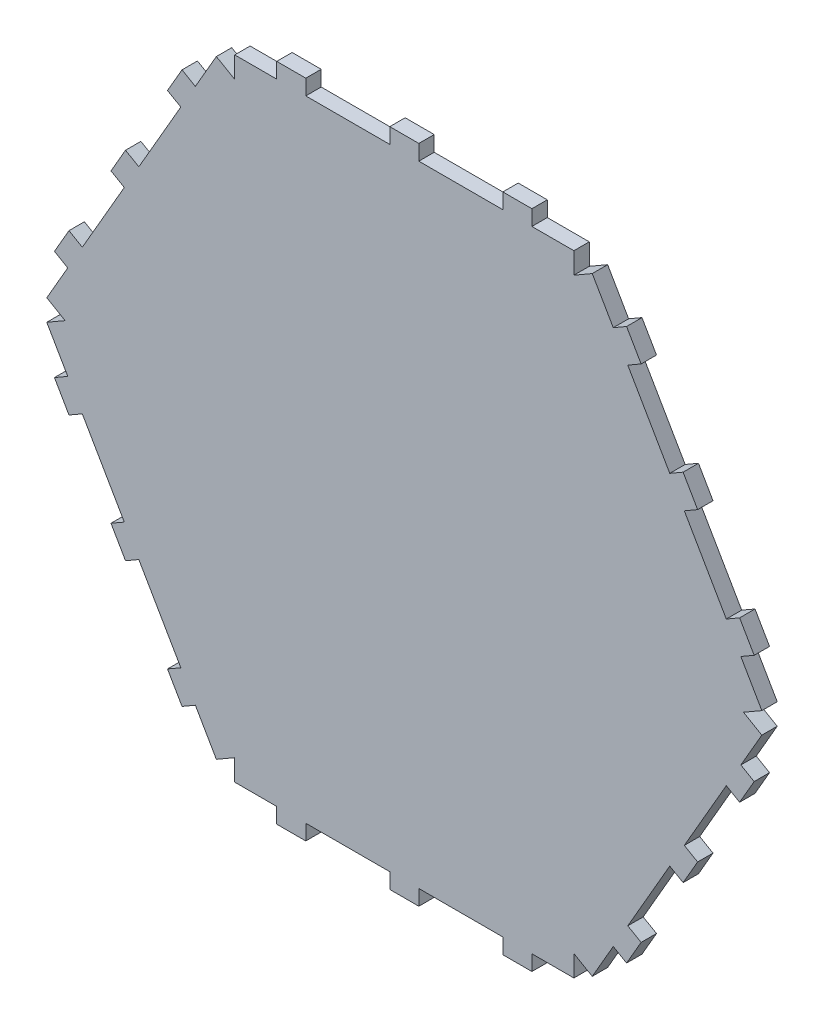
SolidWorks part; units mm, degrees
ref_plane "Front Plane" through (0, 0, 0) normal (0, 0, 1) x (1, 0, 0)
ref_plane "Top Plane" through (0, 0, 0) normal (0, 1, 0) x (1, 0, 0)
ref_plane "Right Plane" through (0, 0, 0) normal (1, 0, 0) x (0, 0, -1)
sketch "Sketch2" plane through (0, 0, 0) normal (0, 0, 1) x (1, 0, 0)
  line L0 (-35, 65) -> (-35, 60.6218)
  line L1 (35, 65) -> (35, 60.6218)
  line L2 (-35, 65) -> (-11.6667, 65) construction
  line L3 (-35, 60.6218) -> (35, 60.6218) construction
  line L4 (35, 60.6218) -> (70, 0) construction
  line L5 (70, 0) -> (35, -60.6218) construction
  line L6 (35, -60.6218) -> (-35, -60.6218) construction
  line L7 (0, 87.3633) -> (0, -0.0109) construction
  line L8 (0, 0) -> (44.1971, 0) construction
  line L9 (-11.6667, 65) -> (11.6667, 65) construction
  line L10 (11.6667, 65) -> (35, 65) construction
  line L11 (-23.3333, 65) -> (-23.3333, 68.175) construction
  line L12 (-20.3333, 68.175) -> (-26.3333, 68.175)
  line L13 (-35, -60.6218) -> (-70, 0) construction
  line L14 (-70, 0) -> (-35, 60.6218) construction
  line L15 (-70, 0) -> (59.0387, 0)
  line L16 (-26.3333, 68.175) -> (-26.3333, 65)
  line L17 (-26.3333, 68.175) -> (-20.3333, 68.175)
  line L18 (-20.3333, 68.175) -> (-20.3333, 65)
  line L19 (-11.6667, 137.7104) -> (-11.6667, 152.546) construction
  line L20 (11.6667, 137.7104) -> (11.6667, 152.546) construction
  line L21 (-26.3333, 68.175) -> (-26.3333, 65)
  line L22 (-20.3333, 68.175) -> (-20.3333, 65)
  line L23 (-26.3333, 68.175) -> (-26.3333, 65)
  line L24 (-20.3333, 68.175) -> (-20.3333, 65)
  line L25 (-26.3333, 68.175) -> (-26.3333, 65)
  line L26 (-20.3333, 68.175) -> (-20.3333, 65)
  line L27 (-26.3333, 68.175) -> (-26.3333, 65)
  line L28 (-20.3333, 68.175) -> (-20.3333, 65)
  line L29 (-26.3333, 68.175) -> (-26.3333, 65)
  line L30 (-20.3333, 68.175) -> (-20.3333, 65)
  line L31 (-26.3333, 68.175) -> (-26.3333, 65)
  line L32 (-20.3333, 68.175) -> (-20.3333, 65)
  line L33 (-26.3333, 68.175) -> (-26.3333, 65)
  line L34 (-20.3333, 68.175) -> (-20.3333, 65)
  line L35 (-26.3333, 68.175) -> (-26.3333, 65)
  line L36 (-20.3333, 68.175) -> (-20.3333, 65)
  line L37 (-26.3333, 68.175) -> (-26.3333, 65)
  line L38 (-20.3333, 68.175) -> (-20.3333, 65)
  line L39 (-26.3333, 68.175) -> (-26.3333, 65)
  line L40 (-20.3333, 68.175) -> (-20.3333, 65)
  line L41 (-26.3333, 68.175) -> (-26.3333, 65)
  line L42 (-20.3333, 68.175) -> (-20.3333, 65)
  line L43 (-26.3333, 68.175) -> (-26.3333, 65)
  line L44 (-20.3333, 68.175) -> (-20.3333, 65)
  line L45 (-26.3333, 68.175) -> (-26.3333, 65)
  line L46 (-20.3333, 68.175) -> (-20.3333, 65)
  line L47 (-26.3333, 68.175) -> (-26.3333, 65)
  line L48 (-20.3333, 68.175) -> (-20.3333, 65)
  line L49 (-26.3333, 68.175) -> (-26.3333, 65)
  line L50 (-20.3333, 68.175) -> (-20.3333, 65)
  line L51 (-26.3333, 68.175) -> (-26.3333, 65)
  line L52 (-20.3333, 68.175) -> (-20.3333, 65)
  line L53 (-26.3333, 68.175) -> (-26.3333, 65)
  line L54 (-20.3333, 68.175) -> (-20.3333, 65)
  line L55 (-26.3333, 68.175) -> (-26.3333, 65)
  line L56 (-20.3333, 68.175) -> (-20.3333, 65)
  line L57 (-26.3333, 68.175) -> (-26.3333, 65)
  line L58 (-20.3333, 68.175) -> (-20.3333, 65)
  line L59 (-26.3333, 68.175) -> (-26.3333, 65)
  line L60 (-20.3333, 68.175) -> (-20.3333, 65)
  line L61 (-26.3333, 68.175) -> (-26.3333, 65)
  line L62 (-20.3333, 68.175) -> (-20.3333, 65)
  line L63 (-26.3333, 68.175) -> (-26.3333, 65)
  line L64 (-20.3333, 68.175) -> (-20.3333, 65)
  line L65 (-26.3333, 68.175) -> (-26.3333, 65)
  line L66 (-20.3333, 68.175) -> (-20.3333, 65)
  line L67 (-26.3333, 68.175) -> (-26.3333, 65)
  line L68 (-20.3333, 68.175) -> (-20.3333, 65)
  line L69 (-26.3333, 68.175) -> (-26.3333, 65)
  line L70 (-20.3333, 68.175) -> (-20.3333, 65)
  line L71 (-26.3333, 68.175) -> (-26.3333, 65)
  line L72 (-20.3333, 68.175) -> (-20.3333, 65)
  line L73 (-26.3333, 68.175) -> (-26.3333, 65)
  line L74 (-20.3333, 68.175) -> (-20.3333, 65)
  line L75 (-26.3333, 68.175) -> (-26.3333, 65)
  line L76 (-20.3333, 68.175) -> (-20.3333, 65)
  line L77 (-26.3333, 68.175) -> (-26.3333, 65)
  line L78 (-20.3333, 68.175) -> (-20.3333, 65)
  line L79 (-26.3333, 68.175) -> (-26.3333, 65)
  line L80 (-20.3333, 68.175) -> (-20.3333, 65)
  line L81 (-26.3333, 68.175) -> (-26.3333, 65)
  line L82 (-20.3333, 68.175) -> (-20.3333, 65)
  line L83 (0, 65) -> (0, 68.175) construction
  line L84 (-3, 68.175) -> (-3, 65)
  line L85 (3, 68.175) -> (3, 65)
  line L86 (-3, 68.175) -> (-3, 65)
  line L87 (3, 68.175) -> (3, 65)
  line L88 (-3, 68.175) -> (-3, 65)
  line L89 (3, 68.175) -> (3, 65)
  line L90 (-3, 68.175) -> (-3, 65)
  line L91 (3, 68.175) -> (3, 65)
  line L92 (-3, 68.175) -> (-3, 65)
  line L93 (3, 68.175) -> (3, 65)
  line L94 (-3, 68.175) -> (-3, 65)
  line L95 (3, 68.175) -> (3, 65)
  line L96 (-3, 68.175) -> (-3, 65)
  line L97 (3, 68.175) -> (3, 65)
  line L98 (-3, 68.175) -> (-3, 65)
  line L99 (3, 68.175) -> (3, 65)
  line L100 (-3, 68.175) -> (-3, 65)
  line L101 (3, 68.175) -> (3, 65)
  line L102 (-3, 68.175) -> (-3, 65)
  line L103 (3, 68.175) -> (3, 65)
  line L104 (-3, 68.175) -> (-3, 65)
  line L105 (3, 68.175) -> (3, 65)
  line L106 (-3, 68.175) -> (-3, 65)
  line L107 (3, 68.175) -> (3, 65)
  line L108 (-3, 68.175) -> (-3, 65)
  line L109 (3, 68.175) -> (3, 65)
  line L110 (-3, 68.175) -> (-3, 65)
  line L111 (3, 68.175) -> (3, 65)
  line L112 (-3, 68.175) -> (-3, 65)
  line L113 (3, 68.175) -> (3, 65)
  line L114 (-3, 68.175) -> (-3, 65)
  line L115 (3, 68.175) -> (3, 65)
  line L116 (-3, 68.175) -> (-3, 65)
  line L117 (3, 68.175) -> (3, 65)
  line L118 (-3, 68.175) -> (-3, 65)
  line L119 (3, 68.175) -> (3, 65)
  line L120 (-3, 68.175) -> (-3, 65)
  line L121 (3, 68.175) -> (3, 65)
  line L122 (-3, 68.175) -> (-3, 65)
  line L123 (3, 68.175) -> (3, 65)
  line L124 (-3, 68.175) -> (-3, 65)
  line L125 (3, 68.175) -> (3, 65)
  line L126 (-3, 68.175) -> (-3, 65)
  line L127 (3, 68.175) -> (3, 65)
  line L128 (-3, 68.175) -> (-3, 65)
  line L129 (3, 68.175) -> (3, 65)
  line L130 (-3, 68.175) -> (-3, 65)
  line L131 (3, 68.175) -> (3, 65)
  line L132 (-3, 68.175) -> (-3, 65)
  line L133 (3, 68.175) -> (3, 65)
  line L134 (-3, 68.175) -> (-3, 65)
  line L135 (3, 68.175) -> (3, 65)
  line L136 (-3, 68.175) -> (-3, 65)
  line L137 (3, 68.175) -> (3, 65)
  line L138 (-3, 68.175) -> (-3, 65)
  line L139 (3, 68.175) -> (3, 65)
  line L140 (-3, 68.175) -> (-3, 65)
  line L141 (3, 68.175) -> (3, 65)
  line L142 (-3, 68.175) -> (-3, 65)
  line L143 (3, 68.175) -> (3, 65)
  line L144 (-3, 68.175) -> (-3, 65)
  line L145 (3, 68.175) -> (3, 65)
  line L146 (-3, 68.175) -> (-3, 65)
  line L147 (3, 68.175) -> (-3, 68.175)
  line L148 (3, 68.175) -> (3, 65)
  line L149 (-3, 68.175) -> (3, 68.175)
  line L150 (-3, 68.175) -> (-3, 65)
  line L151 (3, 68.175) -> (3, 65)
  line L152 (-3, 68.175) -> (-3, 65)
  line L153 (3, 68.175) -> (3, 65)
  line L154 (-3, 68.175) -> (-3, 65)
  line L155 (3, 68.175) -> (3, 65)
  line L156 (-3, 68.175) -> (-3, 65)
  line L157 (3, 68.175) -> (3, 65)
  line L158 (-3, 68.175) -> (-3, 65)
  line L159 (3, 68.175) -> (3, 65)
  line L160 (-3, 68.175) -> (-3, 65)
  line L161 (3, 68.175) -> (3, 65)
  line L162 (-3, 68.175) -> (-3, 65)
  line L163 (3, 68.175) -> (3, 65)
  line L164 (-3, 68.175) -> (-3, 65)
  line L165 (3, 68.175) -> (3, 65)
  line L166 (-3, 68.175) -> (-3, 65)
  line L167 (3, 68.175) -> (3, 65)
  line L168 (-3, 68.175) -> (-3, 65)
  line L169 (3, 68.175) -> (3, 65)
  line L170 (-3, 68.175) -> (-3, 65)
  line L171 (3, 68.175) -> (3, 65)
  line L172 (-3, 68.175) -> (-3, 65)
  line L173 (3, 68.175) -> (3, 65)
  line L174 (-3, 68.175) -> (-3, 65)
  line L175 (3, 68.175) -> (3, 65)
  line L176 (-3, 68.175) -> (-3, 65)
  line L177 (3, 68.175) -> (3, 65)
  line L178 (-3, 68.175) -> (-3, 65)
  line L179 (3, 68.175) -> (3, 65)
  line L180 (-3, 68.175) -> (-3, 65)
  line L181 (3, 68.175) -> (3, 65)
  line L182 (-3, 68.175) -> (-3, 65)
  line L183 (3, 68.175) -> (3, 65)
  line L184 (-3, 68.175) -> (-3, 65)
  line L185 (3, 68.175) -> (3, 65)
  line L186 (-3, 68.175) -> (-3, 65)
  line L187 (3, 68.175) -> (3, 65)
  line L188 (-3, 68.175) -> (-3, 65)
  line L189 (3, 68.175) -> (3, 65)
  line L190 (-3, 68.175) -> (-3, 65)
  line L191 (3, 68.175) -> (3, 65)
  line L192 (-3, 68.175) -> (-3, 65)
  line L193 (3, 68.175) -> (3, 65)
  line L194 (-3, 68.175) -> (-3, 65)
  line L195 (3, 68.175) -> (3, 65)
  line L196 (-3, 68.175) -> (-3, 65)
  line L197 (3, 68.175) -> (3, 65)
  line L198 (-3, 68.175) -> (-3, 65)
  line L199 (3, 68.175) -> (3, 65)
  line L200 (-3, 68.175) -> (-3, 65)
  line L201 (3, 68.175) -> (3, 65)
  line L202 (-3, 68.175) -> (-3, 65)
  line L203 (3, 68.175) -> (3, 65)
  line L204 (-3, 68.175) -> (-3, 65)
  line L205 (3, 68.175) -> (3, 65)
  line L206 (-3, 68.175) -> (-3, 65)
  line L207 (3, 68.175) -> (3, 65)
  line L208 (-3, 68.175) -> (-3, 65)
  line L209 (3, 68.175) -> (3, 65)
  line L210 (-3, 68.175) -> (-3, 65)
  line L211 (3, 68.175) -> (3, 65)
  line L212 (-3, 68.175) -> (-3, 65)
  line L213 (3, 68.175) -> (3, 65)
  line L214 (23.3333, 65) -> (23.3333, 68.175) construction
  line L215 (20.3333, 68.175) -> (20.3333, 65)
  line L216 (26.3333, 68.175) -> (26.3333, 65)
  line L217 (20.3333, 68.175) -> (20.3333, 65)
  line L218 (26.3333, 68.175) -> (26.3333, 65)
  line L219 (20.3333, 68.175) -> (20.3333, 65)
  line L220 (26.3333, 68.175) -> (26.3333, 65)
  line L221 (20.3333, 68.175) -> (20.3333, 65)
  line L222 (26.3333, 68.175) -> (26.3333, 65)
  line L223 (20.3333, 68.175) -> (20.3333, 65)
  line L224 (26.3333, 68.175) -> (26.3333, 65)
  line L225 (20.3333, 68.175) -> (20.3333, 65)
  line L226 (26.3333, 68.175) -> (26.3333, 65)
  line L227 (20.3333, 68.175) -> (20.3333, 65)
  line L228 (26.3333, 68.175) -> (26.3333, 65)
  line L229 (20.3333, 68.175) -> (20.3333, 65)
  line L230 (26.3333, 68.175) -> (26.3333, 65)
  line L231 (20.3333, 68.175) -> (20.3333, 65)
  line L232 (26.3333, 68.175) -> (26.3333, 65)
  line L233 (20.3333, 68.175) -> (20.3333, 65)
  line L234 (26.3333, 68.175) -> (26.3333, 65)
  line L235 (20.3333, 68.175) -> (20.3333, 65)
  line L236 (26.3333, 68.175) -> (26.3333, 65)
  line L237 (20.3333, 68.175) -> (20.3333, 65)
  line L238 (26.3333, 68.175) -> (26.3333, 65)
  line L239 (20.3333, 68.175) -> (20.3333, 65)
  line L240 (26.3333, 68.175) -> (26.3333, 65)
  line L241 (20.3333, 68.175) -> (20.3333, 65)
  line L242 (26.3333, 68.175) -> (26.3333, 65)
  line L243 (20.3333, 68.175) -> (20.3333, 65)
  line L244 (26.3333, 68.175) -> (26.3333, 65)
  line L245 (20.3333, 68.175) -> (20.3333, 65)
  line L246 (26.3333, 68.175) -> (26.3333, 65)
  line L247 (20.3333, 68.175) -> (20.3333, 65)
  line L248 (26.3333, 68.175) -> (26.3333, 65)
  line L249 (20.3333, 68.175) -> (20.3333, 65)
  line L250 (26.3333, 68.175) -> (26.3333, 65)
  line L251 (20.3333, 68.175) -> (20.3333, 65)
  line L252 (26.3333, 68.175) -> (26.3333, 65)
  line L253 (20.3333, 68.175) -> (20.3333, 65)
  line L254 (26.3333, 68.175) -> (26.3333, 65)
  line L255 (20.3333, 68.175) -> (20.3333, 65)
  line L256 (26.3333, 68.175) -> (26.3333, 65)
  line L257 (20.3333, 68.175) -> (20.3333, 65)
  line L258 (26.3333, 68.175) -> (26.3333, 65)
  line L259 (20.3333, 68.175) -> (20.3333, 65)
  line L260 (26.3333, 68.175) -> (26.3333, 65)
  line L261 (20.3333, 68.175) -> (20.3333, 65)
  line L262 (26.3333, 68.175) -> (26.3333, 65)
  line L263 (20.3333, 68.175) -> (20.3333, 65)
  line L264 (26.3333, 68.175) -> (26.3333, 65)
  line L265 (20.3333, 68.175) -> (20.3333, 65)
  line L266 (26.3333, 68.175) -> (26.3333, 65)
  line L267 (20.3333, 68.175) -> (20.3333, 65)
  line L268 (26.3333, 68.175) -> (26.3333, 65)
  line L269 (20.3333, 68.175) -> (20.3333, 65)
  line L270 (26.3333, 68.175) -> (26.3333, 65)
  line L271 (20.3333, 68.175) -> (20.3333, 65)
  line L272 (26.3333, 68.175) -> (26.3333, 65)
  line L273 (20.3333, 68.175) -> (20.3333, 65)
  line L274 (26.3333, 68.175) -> (26.3333, 65)
  line L275 (20.3333, 68.175) -> (20.3333, 65)
  line L276 (26.3333, 68.175) -> (26.3333, 65)
  line L277 (20.3333, 68.175) -> (20.3333, 65)
  line L278 (26.3333, 68.175) -> (26.3333, 65)
  line L279 (26.3333, 68.175) -> (20.3333, 68.175)
  line L280 (20.3333, 68.175) -> (20.3333, 65)
  line L281 (20.3333, 68.175) -> (26.3333, 68.175)
  line L282 (26.3333, 68.175) -> (26.3333, 65)
  line L283 (20.3333, 68.175) -> (20.3333, 65)
  line L284 (26.3333, 68.175) -> (26.3333, 65)
  line L285 (20.3333, 68.175) -> (20.3333, 65)
  line L286 (26.3333, 68.175) -> (26.3333, 65)
  line L287 (20.3333, 68.175) -> (20.3333, 65)
  line L288 (26.3333, 68.175) -> (26.3333, 65)
  line L289 (20.3333, 68.175) -> (20.3333, 65)
  line L290 (26.3333, 68.175) -> (26.3333, 65)
  line L291 (20.3333, 68.175) -> (20.3333, 65)
  line L292 (26.3333, 68.175) -> (26.3333, 65)
  line L293 (20.3333, 68.175) -> (20.3333, 65)
  line L294 (26.3333, 68.175) -> (26.3333, 65)
  line L295 (20.3333, 68.175) -> (20.3333, 65)
  line L296 (26.3333, 68.175) -> (26.3333, 65)
  line L297 (20.3333, 68.175) -> (20.3333, 65)
  line L298 (26.3333, 68.175) -> (26.3333, 65)
  line L299 (20.3333, 68.175) -> (20.3333, 65)
  line L300 (26.3333, 68.175) -> (26.3333, 65)
  line L301 (20.3333, 68.175) -> (20.3333, 65)
  line L302 (26.3333, 68.175) -> (26.3333, 65)
  line L303 (20.3333, 68.175) -> (20.3333, 65)
  line L304 (26.3333, 68.175) -> (26.3333, 65)
  line L305 (20.3333, 68.175) -> (20.3333, 65)
  line L306 (26.3333, 68.175) -> (26.3333, 65)
  line L307 (20.3333, 68.175) -> (20.3333, 65)
  line L308 (26.3333, 68.175) -> (26.3333, 65)
  line L309 (20.3333, 68.175) -> (20.3333, 65)
  line L310 (26.3333, 68.175) -> (26.3333, 65)
  line L311 (20.3333, 68.175) -> (20.3333, 65)
  line L312 (26.3333, 68.175) -> (26.3333, 65)
  line L313 (20.3333, 68.175) -> (20.3333, 65)
  line L314 (26.3333, 68.175) -> (26.3333, 65)
  line L315 (20.3333, 68.175) -> (20.3333, 65)
  line L316 (26.3333, 68.175) -> (26.3333, 65)
  line L317 (20.3333, 68.175) -> (20.3333, 65)
  line L318 (26.3333, 68.175) -> (26.3333, 65)
  line L319 (20.3333, 68.175) -> (20.3333, 65)
  line L320 (26.3333, 68.175) -> (26.3333, 65)
  line L321 (20.3333, 68.175) -> (20.3333, 65)
  line L322 (26.3333, 68.175) -> (26.3333, 65)
  line L323 (20.3333, 68.175) -> (20.3333, 65)
  line L324 (26.3333, 68.175) -> (26.3333, 65)
  line L325 (20.3333, 68.175) -> (20.3333, 65)
  line L326 (26.3333, 68.175) -> (26.3333, 65)
  line L327 (20.3333, 68.175) -> (20.3333, 65)
  line L328 (26.3333, 68.175) -> (26.3333, 65)
  line L329 (20.3333, 68.175) -> (20.3333, 65)
  line L330 (26.3333, 68.175) -> (26.3333, 65)
  line L331 (20.3333, 68.175) -> (20.3333, 65)
  line L332 (26.3333, 68.175) -> (26.3333, 65)
  line L333 (20.3333, 68.175) -> (20.3333, 65)
  line L334 (26.3333, 68.175) -> (26.3333, 65)
  line L335 (20.3333, 68.175) -> (20.3333, 65)
  line L336 (26.3333, 68.175) -> (26.3333, 65)
  line L337 (20.3333, 68.175) -> (20.3333, 65)
  line L338 (26.3333, 68.175) -> (26.3333, 65)
  line L339 (20.3333, 68.175) -> (20.3333, 65)
  line L340 (26.3333, 68.175) -> (26.3333, 65)
  line L341 (20.3333, 68.175) -> (20.3333, 65)
  line L342 (26.3333, 68.175) -> (26.3333, 65)
  line L343 (20.3333, 68.175) -> (20.3333, 65)
  line L344 (26.3333, 68.175) -> (26.3333, 65)
  line L345 (-35, 65) -> (-26.3333, 65)
  line L346 (-20.3333, 65) -> (-3, 65)
  line L347 (3, 65) -> (20.3333, 65)
  line L348 (26.3333, 65) -> (35, 65)
  line L349 (45.8746, 56.8928) -> (43.125, 55.3053)
  line L350 (48.8746, 51.6967) -> (45.8746, 56.8928)
  line L351 (48.8746, 51.6967) -> (46.125, 50.1092)
  line L352 (46.125, 50.1092) -> (54.7917, 35.0981)
  line L353 (57.5413, 36.6856) -> (54.7917, 35.0981)
  line L354 (60.5413, 31.4894) -> (57.5413, 36.6856)
  line L355 (60.5413, 31.4894) -> (57.7917, 29.9019)
  line L356 (57.7917, 29.9019) -> (66.4583, 14.8908)
  line L357 (69.2079, 16.4783) -> (66.4583, 14.8908)
  line L358 (72.2079, 11.2822) -> (69.2079, 16.4783)
  line L359 (72.2079, 11.2822) -> (69.4583, 9.6947)
  line L360 (69.4583, 9.6947) -> (73.7917, 2.1891)
  line L361 (38.7917, 62.8109) -> (43.125, 55.3053)
  line L362 (38.7917, 62.8109) -> (35, 60.6218)
  line L363 (73.7917, 2.1891) -> (70, 0)
  line L364 (72.2079, -11.2822) -> (69.4583, -9.6947)
  line L365 (69.2079, -16.4783) -> (72.2079, -11.2822)
  line L366 (69.2079, -16.4783) -> (66.4583, -14.8908)
  line L367 (66.4583, -14.8908) -> (57.7917, -29.9019)
  line L368 (60.5413, -31.4894) -> (57.7917, -29.9019)
  line L369 (57.5413, -36.6856) -> (60.5413, -31.4894)
  line L370 (57.5413, -36.6856) -> (54.7917, -35.0981)
  line L371 (54.7917, -35.0981) -> (46.125, -50.1092)
  line L372 (48.8746, -51.6967) -> (46.125, -50.1092)
  line L373 (45.8746, -56.8928) -> (48.8746, -51.6967)
  line L374 (45.8746, -56.8928) -> (43.125, -55.3053)
  line L375 (43.125, -55.3053) -> (38.7917, -62.8109)
  line L376 (73.7917, -2.1891) -> (69.4583, -9.6947)
  line L377 (73.7917, -2.1891) -> (70, 0)
  line L378 (38.7917, -62.8109) -> (35, -60.6218)
  line L379 (26.3333, -68.175) -> (26.3333, -65)
  line L380 (20.3333, -68.175) -> (26.3333, -68.175)
  line L381 (20.3333, -68.175) -> (20.3333, -65)
  line L382 (20.3333, -65) -> (3, -65)
  line L383 (3, -68.175) -> (3, -65)
  line L384 (-3, -68.175) -> (3, -68.175)
  line L385 (-3, -68.175) -> (-3, -65)
  line L386 (-3, -65) -> (-20.3333, -65)
  line L387 (-20.3333, -68.175) -> (-20.3333, -65)
  line L388 (-26.3333, -68.175) -> (-20.3333, -68.175)
  line L389 (-26.3333, -68.175) -> (-26.3333, -65)
  line L390 (-26.3333, -65) -> (-35, -65)
  line L391 (35, -65) -> (26.3333, -65)
  line L392 (35, -65) -> (35, -60.6218)
  line L393 (-35, -65) -> (-35, -60.6218)
  line L394 (-45.8746, -56.8928) -> (-43.125, -55.3053)
  line L395 (-48.8746, -51.6967) -> (-45.8746, -56.8928)
  line L396 (-48.8746, -51.6967) -> (-46.125, -50.1092)
  line L397 (-46.125, -50.1092) -> (-54.7917, -35.0981)
  line L398 (-57.5413, -36.6856) -> (-54.7917, -35.0981)
  line L399 (-60.5413, -31.4894) -> (-57.5413, -36.6856)
  line L400 (-60.5413, -31.4894) -> (-57.7917, -29.9019)
  line L401 (-57.7917, -29.9019) -> (-66.4583, -14.8908)
  line L402 (-69.2079, -16.4783) -> (-66.4583, -14.8908)
  line L403 (-72.2079, -11.2822) -> (-69.2079, -16.4783)
  line L404 (-72.2079, -11.2822) -> (-69.4583, -9.6947)
  line L405 (-69.4583, -9.6947) -> (-73.7917, -2.1891)
  line L406 (-38.7917, -62.8109) -> (-43.125, -55.3053)
  line L407 (-38.7917, -62.8109) -> (-35, -60.6218)
  line L408 (-73.7917, -2.1891) -> (-70, 0)
  line L409 (-72.2079, 11.2822) -> (-69.4583, 9.6947)
  line L410 (-69.2079, 16.4783) -> (-72.2079, 11.2822)
  line L411 (-69.2079, 16.4783) -> (-66.4583, 14.8908)
  line L412 (-66.4583, 14.8908) -> (-57.7917, 29.9019)
  line L413 (-60.5413, 31.4894) -> (-57.7917, 29.9019)
  line L414 (-57.5413, 36.6856) -> (-60.5413, 31.4894)
  line L415 (-57.5413, 36.6856) -> (-54.7917, 35.0981)
  line L416 (-54.7917, 35.0981) -> (-46.125, 50.1092)
  line L417 (-48.8746, 51.6967) -> (-46.125, 50.1092)
  line L418 (-45.8746, 56.8928) -> (-48.8746, 51.6967)
  line L419 (-45.8746, 56.8928) -> (-43.125, 55.3053)
  line L420 (-43.125, 55.3053) -> (-38.7917, 62.8109)
  line L421 (-73.7917, 2.1891) -> (-69.4583, 9.6947)
  line L422 (-73.7917, 2.1891) -> (-70, 0)
  line L423 (-38.7917, 62.8109) -> (-35, 60.6218)
  point P121 (0, 0)
  dimension "D1" = 70
  dimension "D2" = 6
  dimension "D3" = 6
  dimension "D4" = 3.175
  dimension "D5" = 120
  dimension "D6" = 130
extrude "Boss-Extrude1" add sketch "Sketch2" along normal mid plane 3.175 contours L423 L420 L419 L418 L417 L416 L415 L414 L413 L412 L411 L410 L409 L421 L422 L408 L405 L404 L403 L402 L401 L400 L399 L398 L397 L396 L395 L394 L406 L407 L393 L390 L389 L388 L387 L386 L385 L384 L383 L382 L381 L380 L379 L391 L392 L378 L375 L374 L373 region at (-30.6667, 62.9907, 0)
